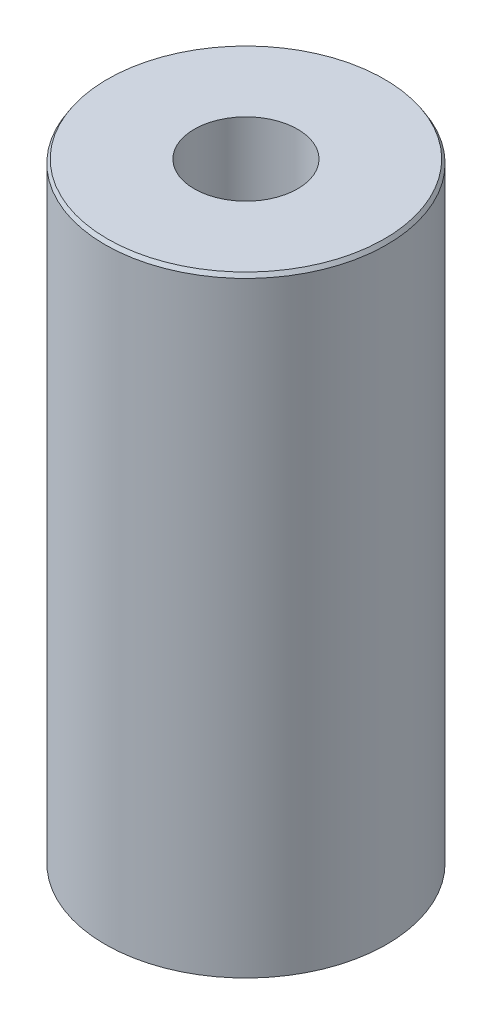
SolidWorks part; units mm, degrees
ref_plane "Front Plane" through (0, 0, 0) normal (0, 0, 1) x (1, 0, 0)
ref_plane "Top Plane" through (0, 0, 0) normal (0, 1, 0) x (1, 0, 0)
ref_plane "Right Plane" through (0, 0, 0) normal (1, 0, 0) x (0, 0, -1)
sketch "Sketch1" plane through (0, 0, 0) normal (0, 1, 0) x (1, 0, 0)
  circle A0 centre (0, 0) radius 37.5
  dimension "SHAFT_OD" = 75
extrude "Boss-Extrude1" add sketch "Sketch1" along normal blind 162.9947
sketch "Sketch2" plane through (0, 0, 0) normal (0, 1, 0) x (1, 0, 0)
  circle A0 centre (0, 0) radius 13.765
  dimension "BORE_D" = 27.5301
extrude "Cut-Extrude1" cut sketch "Sketch2" along normal through all
chamfer "Chamfer1" distance 1.0218 angle 32.034 2 edges at (0, 162.9947, 37.5) (0, 0, 37.5) first distance on face at (0, 162.9947, 37.5) first distance on face at (0, 0, 13.765)
